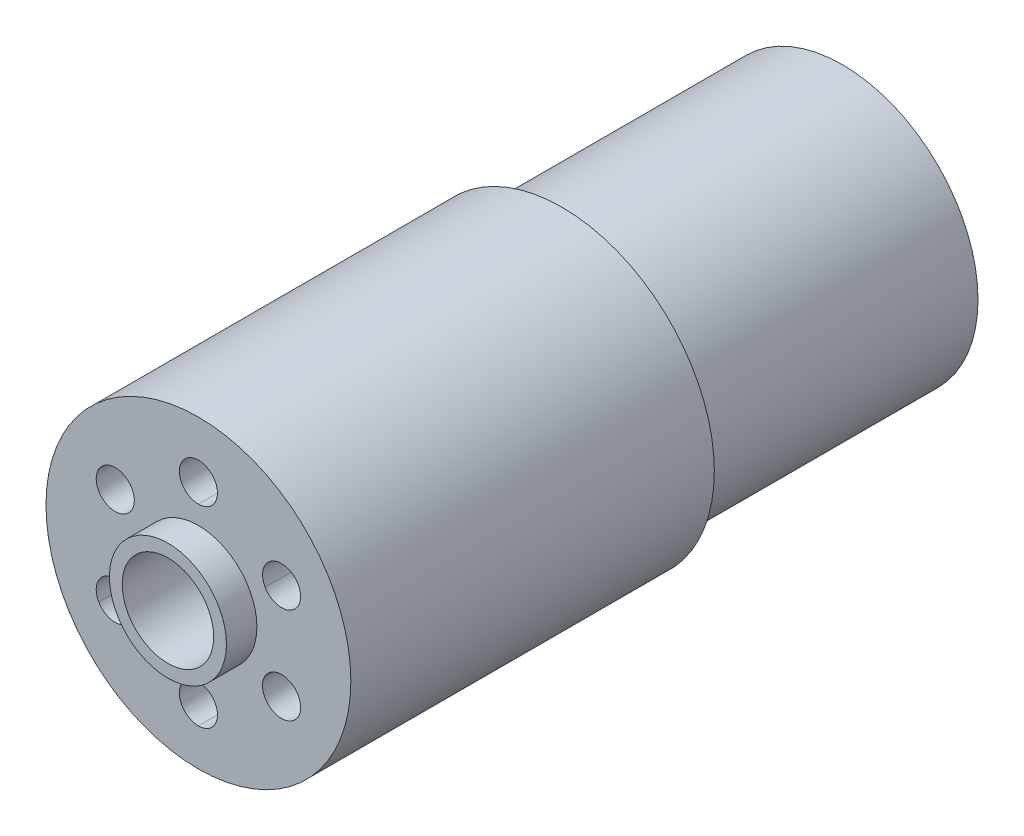
SolidWorks part; units mm, degrees
ref_plane "Front Plane" through (0, 0, 0) normal (0, 0, 1) x (1, 0, 0)
ref_plane "Top Plane" through (0, 0, 0) normal (0, 1, 0) x (1, 0, 0)
ref_plane "Right Plane" through (0, 0, 0) normal (1, 0, 0) x (0, 0, -1)
sketch "Sketch1" plane through (0, 0, 0) normal (0, 0, 1) x (1, 0, 0)
  circle A0 centre (0, 0) radius 25.4
  circle A8 centre (0, 0) radius 9.3953
  point P19 (0, 0)
  dimension "D1" = 50.8
  dimension "D2" = 16.0047
extrude "Boss-Extrude2" add sketch "Sketch1" along normal blind 107.315 contours A0
sketch "Sketch6" plane through (0, 0, 0) normal (0, 0, -1) x (-1, 0, 0)
  circle A0 centre (0, 0) radius 7.62
  circle A1 centre (-13.8581, 8.001) radius 3.175
  circle A2 centre (0, 16.002) radius 3.175
  circle A3 centre (13.8581, 8.001) radius 3.175
  circle A4 centre (13.8581, -8.001) radius 3.175
  circle A5 centre (0, -16.002) radius 3.175
  circle A6 centre (-13.8581, -8.001) radius 3.175
  point P18 (0, 0)
  dimension "D1" = 15.24
  dimension "D2" = 6.35
  dimension "D3" = 16.002
  dimension "D4" = 6
extrude "Cut-Extrude1" cut sketch "Sketch6" against normal blind 108.458
sketch "Sketch7" plane through (0, 0, 0) normal (0, 0, -1) x (-1, 0, 0)
  circle A0 centre (0, 0) radius 22.606
  circle A1 centre (0, 0) radius 25.4 construction
  circle A2 centre (0, 0) radius 25.4
  dimension "D1" = 2.794
extrude "Cut-Extrude2" cut sketch "Sketch7" against normal blind 46.736
sketch "Sketch8" plane through (0, 0, 107.315) normal (0, 0, 1) x (1, 0, 0)
  circle A0 centre (0, 0) radius 7.62
  circle A1 centre (0, 0) radius 9.75
  dimension "D1" = 19.5
  dimension "D2" = 15.24
extrude "Boss-Extrude7" add sketch "Sketch8" along normal blind 5.08
sketch "Sketch9" plane through (0, 0, 0) normal (0, 0, -1) x (-1, 0, 0)
  circle A0 centre (0, 0) radius 7.62
  circle A1 centre (0, 0) radius 9.75
  dimension "D1" = 19.5
  dimension "D2" = 15.24
extrude "Boss-Extrude8" add sketch "Sketch9" along normal blind 5.08
sketch "Sketch10" plane through (0, 0, 0) normal (0, 0, -1) x (-1, 0, 0)
  circle A0 centre (0, 16.002) radius 3.175 construction
  circle A1 centre (0, -16.002) radius 3.175 construction
  circle A2 centre (0, 0) radius 19.177 construction
  circle A3 centre (-13.8581, 8.001) radius 3.175 construction
  circle A4 centre (-13.8581, -8.001) radius 3.175 construction
  circle A5 centre (13.8581, -8.001) radius 3.175 construction
  circle A6 centre (0, 0) radius 12.827 construction
  point P0 (0, 19.177)
  point P1 (0, -19.177)
  point P9 (-16.6078, 9.5885)
  point P10 (-16.6078, -9.5885)
  point P13 (16.6078, -9.5885)
  point P16 (16.6078, 9.5885)
  point P20 (0, 12.827)
  point P21 (-10.9777, 6.6349)
  point P22 (-10.9777, -6.6349)
  point P23 (11.1085, -6.4135)
  point P24 (11.1085, 6.4135)
  point P25 (0, -12.827)
sketch "Sketch11" plane through (0, 0, 107.315) normal (0, 0, 1) x (1, 0, 0)
  point P0 (10.9777, 6.6349)
  point P2 (10.9777, -6.6349)
  point P4 (0, -12.827)
  point P6 (-11.1085, -6.4135)
  point P8 (-11.1085, 6.4135)
  point P10 (0, 12.827)
ref_plane "Plane1" through (0, 0, 0) normal (-1, 0, 0) x (0, 0, 1)
ref_plane "Plane3" through (0, 0, 0) normal (-0.5, -0.866, 0) x (-0.866, 0.5, 0)
ref_plane "Plane6" through (0, 0, 0) normal (0.5, -0.866, 0) x (-0.866, -0.5, 0)
split line "Split Line1"
split line "Split Line2"
split line "Split Line3"
ref_axis "Axis1" through (0, 0, 112.395) along (0, 0, -1)
